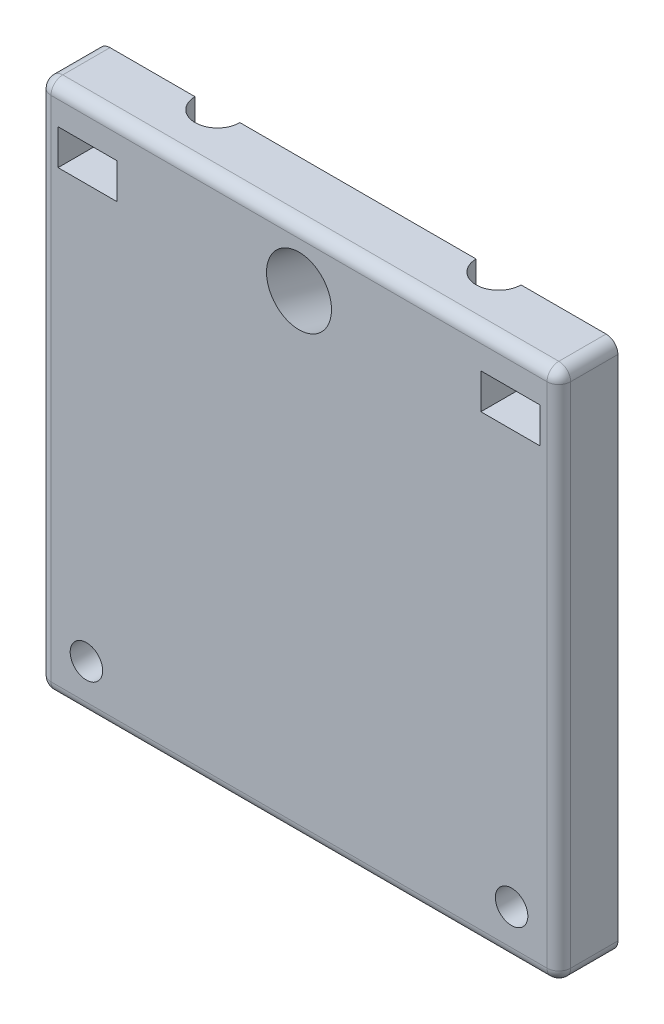
SolidWorks part; units mm, degrees
ref_plane "Front Plane" through (0, 0, 0) normal (0, 0, 1) x (1, 0, 0)
ref_plane "Top Plane" through (0, 0, 0) normal (0, 1, 0) x (1, 0, 0)
ref_plane "Right Plane" through (0, 0, 0) normal (1, 0, 0) x (0, 0, -1)
sketch "Sketch1" plane through (0, 0, 0) normal (0, 0, 1) x (1, 0, 0)
  line L1 (-22, 22.5) -> (22, 22.5)
  line L2 (-22, 22.5) -> (-22, -22.5)
  line L3 (-22, -22.5) -> (22, -22.5)
  line L4 (22, 22.5) -> (22, -22.5)
  line L5 (-22, 22.5) -> (22, -22.5) construction
  line L6 (-22, -22.5) -> (22, 22.5) construction
  point P0 (0, 0)
  dimension "D1" = 44
  dimension "D2" = 45
extrude "Base" add sketch "Sketch1" along normal blind 5
sketch "Sketch2" plane through (0, 22.5, 0) normal (0, 1, 0) x (1, 0, 0)
  line L0 (22, 0) -> (-22, 0) construction
  line L1 (-13.8, 0) -> (-10, 0)
  line L2 (0, 0) -> (0, -5) construction
  line L3 (22, -5) -> (-22, -5) construction
  line L4 (13.8, 0) -> (10, 0)
  arc A0 (-13.8, 0) -> (-10, 0) centre (-11.9, 0) ccw
  arc A1 (13.8, 0) -> (10, 0) centre (11.9, 0) cw
  dimension "D1" = 1.9
  dimension "D2" = 11.9
extrude "Wire Grooves" cut sketch "Sketch2" against normal through all
sketch "Sketch4" plane through (0, 0, 0) normal (0, 0, -1) x (-1, 0, 0)
  line L0 (0, 22.5) -> (0, -22.5) construction
  line L1 (-10, 22.5) -> (10, 22.5) construction
  line L2 (10, -22.5) -> (-10, -22.5) construction
  line L3 (-22, 16.5291) -> (22, 16.5291) construction
  line L4 (-22, -22.5) -> (-22, 22.5) construction
  line L5 (22, 22.5) -> (22, -22.5) construction
  dimension "D1" = 5.9709
ref_plane "Screw Insertion Hole Reference" through (0, 1.1072, 4.1323) normal (0, -0.2588, -0.9659) x (-1, 0, 0)
sketch "Sketch3" plane through (0, 0.5961, 4.2692) normal (0, -0.2588, -0.9659) x (-1, 0, 0)
  line L0 (0, 0.5291) -> (0, 22.2625) construction
  line L1 (-10, 22.2625) -> (10, 22.2625) construction
  circle A0 centre (0, 16.2916) radius 2.75
  dimension "D1" = 5.5
  dimension "D2" = 5.9709
extrude "Screw Insertion Hole" cut sketch "Sketch3" against normal through all both and the other way through all
sketch "Sketch5" plane through (0, 0, 0) normal (0, 0, -1) x (-1, 0, 0)
  line L0 (-17.9, 22.5) -> (-17.9, -22.5) construction
  line L1 (-22, 22.5) -> (-13.8, 22.5) construction
  line L2 (-13.8, -22.5) -> (-22, -22.5) construction
  line L3 (0, 22.5) -> (0, -22.5) construction
  line L4 (-10, 22.5) -> (10, 22.5) construction
  line L5 (10, -22.5) -> (-10, -22.5) construction
  line L6 (20.4, 16.5) -> (15.4, 16.5)
  line L7 (-20.4, 19.5) -> (-15.4, 19.5)
  line L8 (-20.4, 19.5) -> (-20.4, 16.5)
  line L9 (-20.4, 16.5) -> (-15.4, 16.5)
  line L10 (-15.4, 19.5) -> (-15.4, 16.5)
  line L11 (-20.4, 19.5) -> (-15.4, 16.5) construction
  line L12 (-20.4, 16.5) -> (-15.4, 19.5) construction
  line L13 (15.4, 19.5) -> (15.4, 16.5)
  line L14 (20.4, 19.5) -> (15.4, 19.5)
  line L15 (20.4, 19.5) -> (20.4, 16.5)
  point P12 (-17.9, 18)
  dimension "D1" = 5
  dimension "D2" = 3
  dimension "D3" = 3
extrude "Zip Tie Slots" cut sketch "Sketch5" against normal through all
sketch "Sketch6" plane through (0, 0, 0) normal (0, 0, -1) x (-1, 0, 0)
  line L0 (-13.8, -22.5) -> (-22, -22.5) construction
  line L1 (-22, -22.5) -> (-22, 22.5) construction
  line L3 (-10, 22.5) -> (10, 22.5) construction
  line L4 (0, 22.5) -> (0, -22.5) construction
  line L5 (10, -22.5) -> (-10, -22.5) construction
  circle A0 centre (-18, -18.5) radius 1.375
  circle A1 centre (18, -18.5) radius 1.375
  dimension "D1" = 2.75
  dimension "D2" = 4
  dimension "D3" = 4
extrude "Mount Clamping Holes" cut sketch "Sketch6" against normal through all
fillet "Edge Fillets" radius 1 8 edges at (-22, 0, 5) (22, 0, 5) (0, -22.5, 5) (0, 22.5, 5) (22, 22.5, 2.5) (22, -22.5, 2.5) (-22, -22.5, 2.5) (-22, 22.5, 2.5)
